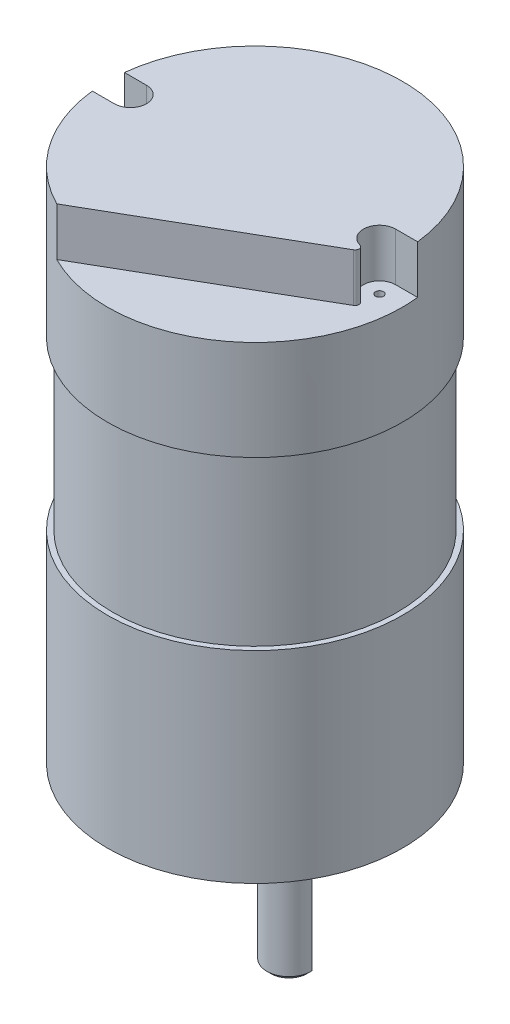
SolidWorks part; units mm, degrees
material "PE High Density"
ref_plane "Front Plane" through (0, 0, 0) normal (0, 0, 1) x (1, 0, 0)
ref_plane "Top Plane" through (0, 0, 0) normal (0, 1, 0) x (1, 0, 0)
ref_plane "Right Plane" through (0, 0, 0) normal (1, 0, 0) x (0, 0, -1)
sketch "Sketch1" plane through (0, 0, 0) normal (0, 0, 1) x (1, 0, 0)
  line L0 (0, 41.1329) -> (0, -49.1088) construction
  line L1 (0, 32.15) -> (18.35, 32.15)
  line L2 (18.35, 32.15) -> (18.35, 13.75)
  line L3 (18.35, 13.75) -> (17.7, 13.75)
  line L4 (17.7, 13.75) -> (17.7, -7.05)
  line L5 (17.7, -7.05) -> (18.35, -7.05)
  line L6 (18.35, -7.05) -> (18.35, -32.15)
  line L7 (18.35, -32.15) -> (0, -32.15)
  line L8 (0, 32.15) -> (0, -32.15)
  point P11 (0, 0)
  dimension "D1" = 36.7
  dimension "D2" = 18.4
  dimension "D3" = 35.4
  dimension "D4" = 25.1
  dimension "D5" = 64.3
revolve "Revolve1" add sketch "Sketch1" angle 360 about L0
sketch "Sketch2" plane through (0, 32.15, 0) normal (0, 1, 0) x (1, 0, 0)
  line L0 (-18.35, 0) -> (18.35, 0) construction
  line L1 (-15.5, 0) -> (-20.9613, 0) construction
  line L2 (-15.5, -2) -> (-20.9613, -2)
  line L3 (-15.5, 2) -> (-20.9613, 2)
  line L4 (15.4931, 0) -> (18.35, 0) construction
  line L5 (15.4931, 2) -> (18.35, 2)
  line L6 (15.4931, -2) -> (18.35, -2)
  line L7 (-8.2957, -16.3678) -> (18.3228, -0.9996)
  circle A0 centre (0, 0) radius 18.35 construction
  circle A1 centre (0, 0) radius 15.5 construction
  arc A2 (-15.5, -2) -> (-15.5, 2) centre (-15.5, 0) ccw
  arc A3 (-20.9613, 2) -> (-20.9613, -2) centre (-20.9613, 0) ccw
  arc A4 (15.4931, 2) -> (15.4931, -2) centre (15.4931, 0) ccw
  arc A5 (18.35, -2) -> (18.35, 2) centre (18.35, 0) ccw
  arc A6 (-8.2957, -16.3678) -> (18.3202, -1.0461) centre (0, 0) ccw
  point P10 (-18.2306, 0)
  point P16 (16.9216, 0)
  circle M3 centre (0, 0) radius 18.35
  dimension "D1" = 31
  dimension "D2" = 2
  dimension "D3" = 2
  dimension "D4" = 30
  dimension "D5" = 1
extrude "Cut-Extrude3" cut sketch "Sketch2" against normal blind 6 contours L2 A2 L3 M3 | L5 A4 L6 L7 M3 | L7 L6 M3 | L7 L6 M3 region at (-16.0988, 32.15, 0) region at (6.6645, 32.15, 11.6776) region at (16.0148, 32.15, -0.0826) region at (17.721, 32.15, 1.6656)
fillet "Fillet1" radius 0.5 1 edges at (16.5901, 29.15, 2)
sketch "Sketch3" plane through (0, 26.15, 0) normal (0, 1, 0) x (1, 0, 0)
  circle A0 centre (15.4931, 0) radius 0.5
  circle A1 centre (-15.4331, 0) radius 0.5
  dimension "D1" = 1
extrude "Cut-Extrude4" cut sketch "Sketch3" against normal up to surface (33.2 mm away) up to face at (0, -7.05, 17.7)
sketch "Sketch4" plane through (0, -32.15, 0) normal (0, -1, 0) x (1, 0, 0)
  line L0 (-2.3235, -6.5501) -> (3.409, 9.6101) construction
  line L4 (15.1136, 2.8524) -> (-8.2957, 16.3678)
  line L5 (18.2407, -2) -> (15.4931, -2)
  line L6 (-15.5, -2) -> (-18.2407, -2)
  line L7 (-18.2407, 2) -> (-15.5, 2)
  line L8 (15.1136, 2.8524) -> (-8.2957, 16.3678) construction
  line L9 (18.2407, -2) -> (15.4931, -2)
  line L10 (-15.5, -2) -> (-18.2407, -2) construction
  line L11 (-18.2407, 2) -> (-15.5, 2) construction
  circle A0 centre (0, 0) radius 1.05 construction
  circle A1 centre (0, 0) radius 18.35 construction
  circle A2 centre (0, 0) radius 6.95 construction
  circle A3 centre (-2.3235, -6.5501) radius 5.95
  circle A4 centre (0, 0) radius 18.35
  arc A8 (14.9895, 1.9355) -> (15.1136, 2.8524) centre (14.8636, 2.4194) ccw
  arc A9 (14.9895, 1.9355) -> (15.4931, -2) centre (15.4931, 0) ccw
  arc A10 (-18.2407, -2) -> (18.2407, -2) centre (0, 0) ccw
  arc A11 (-15.5, -2) -> (-15.5, 2) centre (-15.5, 0) ccw
  arc A12 (-8.2957, 16.3678) -> (-18.2407, 2) centre (0, 0) ccw
  arc A13 (14.9895, 1.9355) -> (15.1136, 2.8524) centre (14.8636, 2.4194) ccw construction
  arc A14 (14.9895, 1.9355) -> (15.4931, -2) centre (15.4931, 0) ccw construction
  arc A15 (-18.2407, -2) -> (18.2407, -2) centre (0, 0) ccw construction
  arc A16 (-15.5, -2) -> (-15.5, 2) centre (-15.5, 0) ccw construction
  arc A17 (-8.2957, 16.3678) -> (-18.2407, 2) centre (0, 0) ccw construction
  dimension "D1" = 17.3
  dimension "D4" = 11.9
  dimension "D2" = 5.9
  dimension "D3" = 0
extrude "Boss-Extrude1" add sketch "Sketch4" along normal blind 6 contours A3 region at (-2.3235, -32.15, -6.5501)
sketch "Sketch5" plane through (0, -38.15, 0) normal (0, -1, 0) x (1, 0, 0)
  circle A0 centre (-2.3235, -6.5501) radius 2.75
  dimension "D1" = 5.5
extrude "Boss-Extrude2" add sketch "Sketch5" along normal blind 20
chamfer "Chamfer1" distance 0.5 angle 45 1 edges at (-2.3235, -58.15, -9.3001)
sketch "Sketch7" plane through (0, -58.15, 0) normal (0, -1, 0) x (1, 0, 0)
  line L0 (-2.3558, -9.2999) -> (0.4249, -6.6455)
  line L1 (0.4249, -6.6455) -> (1.7515, -8.0352)
  line L2 (1.7515, -8.0352) -> (-1.0292, -10.6896)
  line L3 (-1.0292, -10.6896) -> (-2.3558, -9.2999)
  circle A0 centre (-2.3235, -6.5501) radius 2.75 construction
  circle A1 centre (-2.3235, -6.5501) radius 2.75 construction
extrude "Cut-Extrude5" cut sketch "Sketch7" against normal blind 12
sketch "Sketch8" plane through (0, -32.15, 0) normal (0, -1, 0) x (1, 0, 0)
  arc A0 (1.7846, -10.8543) -> (-8.2256, -7.3034) centre (0, 0) ccw construction
  circle A1 centre (-2.3235, -6.5501) radius 5.95 construction
  arc A2 (1.7846, -10.8543) -> (-8.2256, -7.3034) centre (-2.3235, -6.5501) ccw construction
  arc A3 (-9.4584, -4.0812) -> (4.7724, -9.1292) centre (-2.3235, -6.5501) cw
  arc A4 (5.3426, -9.6155) -> (-10.2076, -4.0994) centre (0, 0) ccw
  arc A5 (4.7724, -9.1292) -> (5.3426, -9.6155) centre (5.1483, -9.2658) ccw
  arc A6 (-9.4584, -4.0812) -> (-10.2076, -4.0994) centre (-9.8364, -3.9504) cw
  point P10 (4.3346, -10.11)
  point P13 (-9.7365, -5.1186)
  dimension "D1" = 22
  dimension "D2" = 1.6
  dimension "D3" = 0.4
extrude "Cut-Extrude6" cut sketch "Sketch8" against normal blind 0.8 contours A3 A4 region at (1.0228, -32.15, 2.8835)
sketch "Sketch9" plane through (0, -32.15, 0) normal (0, -1, 0) x (1, 0, 0)
  line L0 (0, 0) -> (-3.3343, 18.0445) construction
  line L1 (-2.3235, -6.5501) -> (5.0983, 14.3725) construction
  circle A0 centre (0, 0) radius 18.35 construction
  circle A1 centre (0, 0) radius 15.25 construction
  circle A2 centre (0, 15.25) radius 1.5 construction
  circle A3 centre (-2.771, 14.9961) radius 1.5
  circle A4 centre (11.6015, 9.8978) radius 1.5
  circle A5 centre (14.3725, -5.0983) radius 1.5
  circle A6 centre (2.771, -14.9961) radius 1.5
  circle A7 centre (-11.6015, -9.8978) radius 1.5
  circle A8 centre (-14.3725, 5.0983) radius 1.5
  point P27 (0, 0)
  dimension "D1" = 30.5
  dimension "D2" = 3
  dimension "D3" = 30
  dimension "D4" = 6
extrude "Cut-Extrude7" cut sketch "Sketch9" against normal blind 3.2
fillet "Fillet2" radius 0.5 4 edges at (4.8887, -31.35, -9.5702) (0.2006, -31.35, 0.5655) (-9.8266, -31.35, -4.3502) (3.6775, -31.35, 10.3671)
